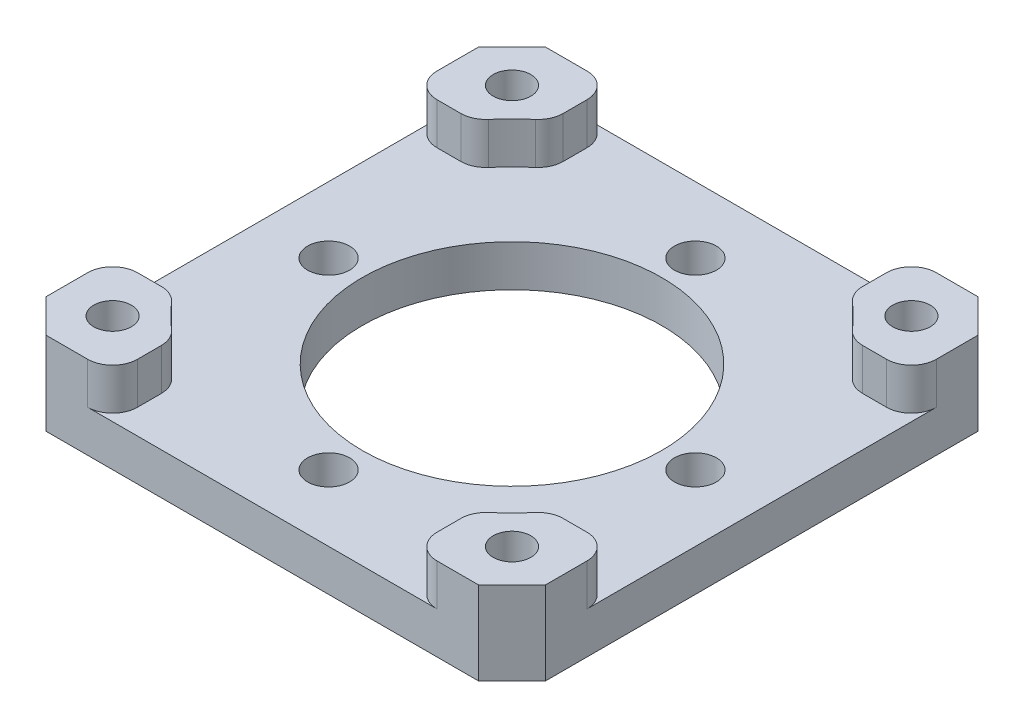
SolidWorks part; units mm, degrees
material "Alum Plate"
ref_plane "Front Plane" through (0, 0, 0) normal (0, 0, 1) x (1, 0, 0)
ref_plane "Top Plane" through (0, 0, 0) normal (0, 1, 0) x (1, 0, 0)
ref_plane "Right Plane" through (0, 0, 0) normal (1, 0, 0) x (0, 0, -1)
other "Bounding Box"
ref_plane "Default Plane" through (0, 2.286, 19.05) normal (0, -1, 0) x (-1, 0, 0)
sketch "Sketch1" plane through (0, 0, 0) normal (0, 1, 0) x (1, 0, 0)
  line L1 (-19.05, 19.05) -> (19.05, 19.05)
  line L2 (-19.05, 19.05) -> (-19.05, -19.05)
  line L3 (-19.05, -19.05) -> (19.05, -19.05)
  line L4 (19.05, 19.05) -> (19.05, -19.05)
  line L5 (-19.05, 19.05) -> (19.05, -19.05) construction
  line L6 (-19.05, -19.05) -> (19.05, 19.05) construction
  circle A0 centre (0, 0) radius 11.43
  point P0 (0, 0)
  dimension "D2" = 22.86
  dimension "D1" = 38.1
extrude "Boss-Extrude1" add sketch "Sketch1" along normal blind 3.175
sketch "Sketch2" plane through (0, 3.175, 0) normal (0, 1, 0) x (1, 0, 0)
  line L0 (0, 0) -> (0, 13.9954) construction
  line L1 (0, 0) -> (15.24, 15.24) construction
  line L2 (15.24, 15.24) -> (19.05, 15.24) construction
  line L3 (19.05, -19.05) -> (19.05, 19.05) construction
  line L4 (15.24, 15.24) -> (15.24, 19.05) construction
  line L5 (19.05, 19.05) -> (-19.05, 19.05) construction
  circle A0 centre (0, 13.9954) radius 1.6002
  circle A1 centre (15.24, 15.24) radius 1.4351
  dimension "D1" = 3.2004
  dimension "D3" = 2.8702
  dimension "D2" = 13.9954
  dimension "D4" = 3.81
extrude "Cut-Extrude1" cut sketch "Sketch2" against normal through all
pattern_circular "CirPattern1" count 4 over 360 about axis through (0, 3.175, 0) along (0, -1, 0) of "Cut-Extrude1"
chamfer "Chamfer1" distance 2.54 angle 45 4 edges at (-19.05, 1.5875, 19.05) (19.05, 1.5875, 19.05) (19.05, 1.5875, -19.05) (-19.05, 1.5875, -19.05)
sketch "Sketch3" plane through (0, 3.175, 0) normal (0, 1, 0) x (1, 0, 0)
  line L0 (-19.05, 11.43) -> (-14.4384, 11.43)
  line L1 (-11.43, 19.05) -> (-11.43, 14.4384)
  line L8 (-19.05, 16.51) -> (-19.05, -16.51)
  line L9 (-19.05, -16.51) -> (-16.51, -19.05)
  line L10 (-16.51, -19.05) -> (16.51, -19.05)
  line L11 (16.51, -19.05) -> (19.05, -16.51)
  line L12 (19.05, -16.51) -> (19.05, 16.51)
  line L13 (19.05, 16.51) -> (16.51, 19.05)
  line L14 (16.51, 19.05) -> (-16.51, 19.05)
  line L15 (-16.51, 19.05) -> (-19.05, 16.51)
  line L16 (-19.05, 16.51) -> (-19.05, 11.43)
  line L22 (-11.43, 19.05) -> (-16.51, 19.05)
  line L23 (-16.51, 19.05) -> (-19.05, 16.51)
  circle A3 centre (-15.24, 15.24) radius 1.4351 construction
  circle A7 centre (-15.24, 15.24) radius 1.4351
  arc A8 (-11.43, 14.4384) -> (-14.4384, 11.43) centre (0, 0) ccw
  circle M10 centre (-15.24, 15.24) radius 1.4351
  line M18 (-19.05, 16.51) -> (-19.05, -16.51)
  line M24 (16.51, 19.05) -> (-16.51, 19.05)
  line M25 (-16.51, 19.05) -> (-19.05, 16.51)
  dimension "D2" = 18.415
  dimension "D3" = 7.62
  dimension "D1" = 0
extrude "Boss-Extrude2" add sketch "Sketch3" along normal blind 3.175 contours A8 M24 M25 M18 M10 region at (-18.9422, 3.175, -13.97)
fillet "Fillet1" radius 1.905 4 edges at (-19.05, 4.7625, -11.43) (-11.43, 4.7625, -19.05) (-11.43, 4.7625, -14.4384) (-14.4384, 4.7625, -11.43)
pattern_circular "CirPattern7" count 4 over 360 about axis through (0, 3.175, 0) along (0, -1, 0) of "Boss-Extrude2", "Fillet1"
equation "\"Unit Measure\"= \"BoundingVolume\" / \"Thickness\"'in^2"
